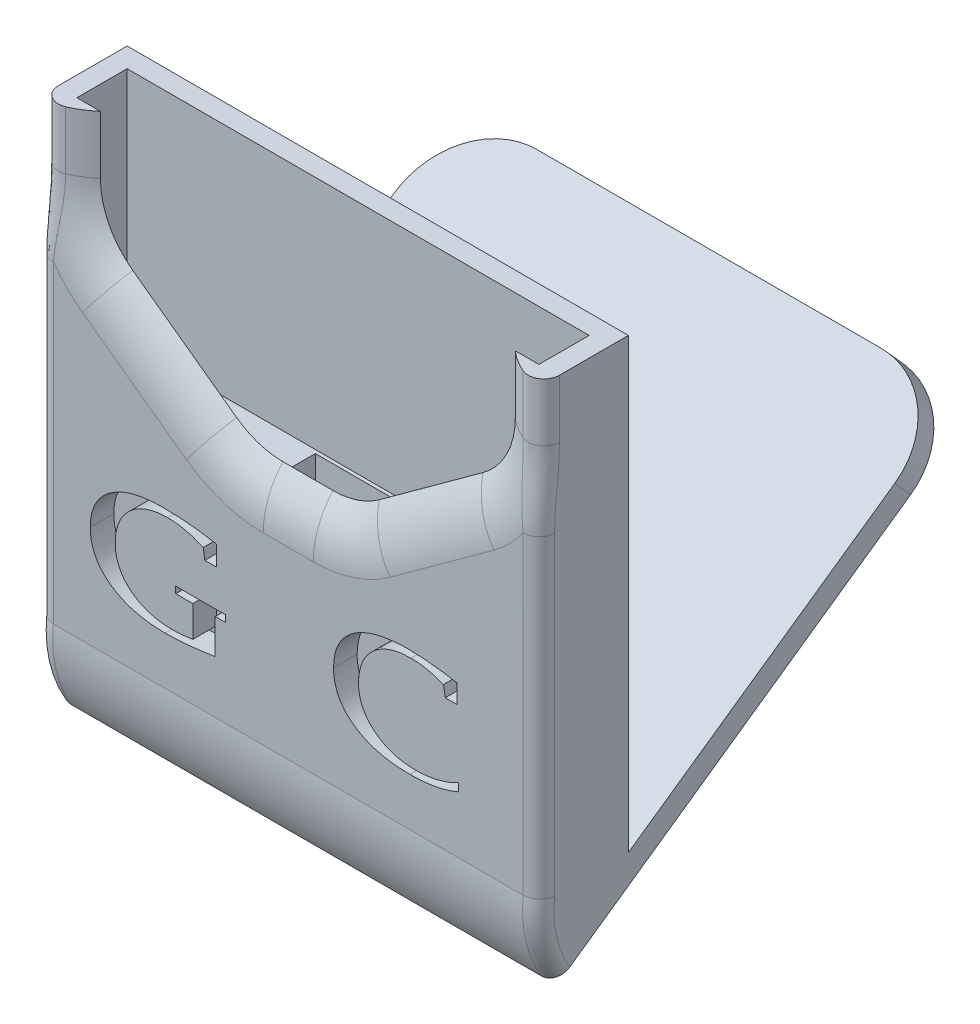
SolidWorks part; units mm, degrees
ref_plane "Front Plane" through (0, 0, 0) normal (0, 0, 1) x (1, 0, 0)
ref_plane "Top Plane" through (0, 0, 0) normal (0, 1, 0) x (1, 0, 0)
ref_plane "Right Plane" through (0, 0, 0) normal (1, 0, 0) x (0, 0, -1)
sketch "Sketch1" plane through (0, 0, 0) normal (0, 1, 0) x (1, 0, 0)
  line L0 (-31.9, 5.7) -> (31.9, 5.7)
  line L1 (-29.4, -3.2) -> (29.4, -3.2)
  line L2 (-29.4, -3.2) -> (-29.4, 3.2)
  line L3 (-29.4, 3.2) -> (29.4, 3.2)
  line L4 (29.4, -3.2) -> (29.4, 3.2)
  line L5 (-29.4, -3.2) -> (29.4, 3.2) construction
  line L6 (-29.4, 3.2) -> (29.4, -3.2) construction
  line L7 (31.9, -5.7) -> (31.9, 5.7)
  line L8 (-31.9, -5.7) -> (31.9, -5.7)
  line L9 (-31.9, -5.7) -> (-31.9, 5.7)
  point P0 (0, 0)
  dimension "D1" = 58.8
  dimension "D2" = 6.4
  dimension "D3" = 2.5
extrude "Boss-Extrude1" add sketch "Sketch1" along normal blind 30
sketch "Sketch2" plane through (0, 0, 5.7) normal (0, 0, 1) x (1, 0, 0)
  line L0 (-31.9, 30) -> (31.9, 30) construction
  line L1 (-26.4, 30) -> (26.4, 30)
  line L2 (-26.4, 30) -> (-26.4, 22.6072)
  line L3 (-3.1854, 3) -> (3.1854, 3)
  line L5 (-31.9, 0) -> (31.9, 0) construction
  line L7 (-31.9, 30) -> (-31.9, 0) construction
  line L8 (-22.2803, 14.5188) -> (-9.0657, 4.9116)
  line L9 (0, 0) -> (0, 33.0481) construction
  line L10 (22.2803, 14.5188) -> (9.0657, 4.9116)
  line L11 (26.4, 30) -> (26.4, 22.6072)
  arc A0 (-26.4, 22.6072) -> (-22.2803, 14.5188) centre (-16.4, 22.6072) ccw
  arc A1 (-3.1854, 3) -> (-9.0657, 4.9116) centre (-3.1854, 13) cw
  arc A2 (3.1854, 3) -> (9.0657, 4.9116) centre (3.1854, 13) ccw
  arc A3 (26.4, 22.6072) -> (22.2803, 14.5188) centre (16.4, 22.6072) cw
  dimension "D5" = 10
  dimension "D4" = 10
  dimension "D1" = 3
  dimension "D3" = 5.5
extrude "Cut-Extrude1" cut sketch "Sketch2" against normal blind 7
sketch "Sketch3" plane through (0, 0, 0) normal (0, -1, 0) x (1, 0, 0)
  line L4 (-31.9, 5.7) -> (-31.9, -5.7)
  line L5 (-31.9, -5.7) -> (31.9, -5.7)
  line L6 (31.9, -5.7) -> (31.9, 5.7)
  line L7 (31.9, 5.7) -> (-31.9, 5.7)
  line L8 (-31.9, 5.7) -> (-31.9, -5.7)
  line L9 (-31.9, -5.7) -> (31.9, -5.7)
  line L10 (31.9, -5.7) -> (31.9, 5.7)
  line L11 (31.9, 5.7) -> (-31.9, 5.7)
  dimension "D1" = 0
extrude "Boss-Extrude2" add sketch "Sketch3" along normal blind 15
sketch "Sketch4" plane through (0, 0, 0) normal (0, 1, 0) x (1, 0, 0)
  line L0 (0, 3.2) -> (0, -12.2085) construction
  line L1 (29.4, 3.2) -> (-29.4, 3.2) construction
  line L3 (-5, -2.75) -> (5, -2.75)
  line L4 (-5, -2.75) -> (-5, 2.75)
  line L5 (-5, 2.75) -> (5, 2.75)
  line L6 (5, -2.75) -> (5, 2.75)
  line L7 (-5, -2.75) -> (5, 2.75) construction
  line L8 (-5, 2.75) -> (5, -2.75) construction
  point P5 (0, 0)
  dimension "D1" = 10
  dimension "D2" = 5.5
extrude "Cut-Extrude2" cut sketch "Sketch4" against normal blind 23
sketch "Sketch5" plane through (0, -15, 0) normal (0, -1, 0) x (1, 0, 0)
  line L0 (-5, 5.7) -> (-31.9, 5.7)
  line L1 (5, -5.7) -> (31.9, -5.7)
  line L2 (-5, 5.7) -> (5, 5.7)
  line L3 (-5, -5.7) -> (-5, 2.75)
  line L4 (31.9, 5.7) -> (-31.9, 5.7)
  line L5 (-31.9, 5.7) -> (-31.9, -5.7)
  line L6 (-31.9, -5.7) -> (31.9, -5.7)
  line L7 (31.9, -5.7) -> (31.9, 5.7)
  line L8 (31.9, 5.7) -> (5, 5.7)
  line L9 (-31.9, 5.7) -> (-31.9, -5.7)
  line L10 (-31.9, -5.7) -> (-5, -5.7)
  line L11 (31.9, -5.7) -> (31.9, 5.7)
  line L12 (-5, 2.75) -> (5, 2.75)
  line L13 (5, 2.75) -> (5, -5.7)
  dimension "D1" = 0
extrude "Boss-Extrude3" add sketch "Sketch5" along normal blind 12
fillet "Fillet1" radius 10 1 edges
sketch "Sketch7" plane through (-31.9, 0, 0) normal (-1, 0, 0) x (0, 0, 1)
  line L0 (-5.7, -27) -> (-23.2919, -14.682)
  line L1 (-5.7, 30) -> (-5.7, -27) construction
  line L2 (-23.2919, -14.682) -> (-47.8532, 2.516)
  line L3 (-25.0126, -17.1395) -> (3.4068, -37.039)
  line L4 (-25.0126, -17.1395) -> (-49.8608, 0.2594)
  line L5 (-47.8532, 2.516) -> (-49.8608, 0.2594)
  line L6 (5.7, -27) -> (-5.7, -27)
  arc A0 (3.4068, -37.039) -> (5.7, -27) centre (-10.444, -28.5936) ccw
  dimension "D1" = 55
  dimension "D2" = 3
  dimension "D3" = 29.9838
extrude "Boss-Extrude4" add sketch "Sketch7" against normal up to surface (63.8 mm away) up to face at (31.9, 1.5, 0)
sketch "Sketch8" plane through (0, 0, -5.7) normal (0, 0, -1) x (-1, 0, 0)
  line L1 (-5, -15) -> (5, -15)
  line L2 (-5, -15) -> (-5, -3)
  line L3 (-5, -3) -> (5, -3)
  line L4 (5, -15) -> (5, -3)
  dimension "D1" = 12
extrude "Cut-Extrude3" cut sketch "Sketch8" against normal blind 6
fillet "Fillet2" radius 10 2 edges at (-31.9, 1.3877, -48.857) (31.9, 1.3877, -48.857)
fillet "Fillet3" radius 10 9 edges at (-26.4, 26.3036, 5.7) (-25.3108, 18.0687, 5.7) (26.4, 26.3036, 5.7) (25.3108, 18.0687, 5.7) (15.673, 9.7152, 5.7) (6.277, 3.4899, 5.7) (0, 3, 5.7) (-6.277, 3.4899, 5.7) (-15.673, 9.7152, 5.7)
fillet "Fillet4" radius 2 8 edges at (-31.9, 26.3036, 5.6377) (31.9, 26.3036, 5.6377) (31.9, -32.2063, 5.3711) (-31.9, -32.2063, 5.3711) (-31.9, -5.1875, 5.7) (31.9, -5.1875, 5.7)
sketch "Sketch9" plane through (0, 0, 5.7) normal (0, 0, 1) x (1, 0, 0)
  text T0 "GC" font "Lucida Fax" height in points 48
extrude "Cut-Extrude4" cut sketch "Sketch9" against normal blind 3
